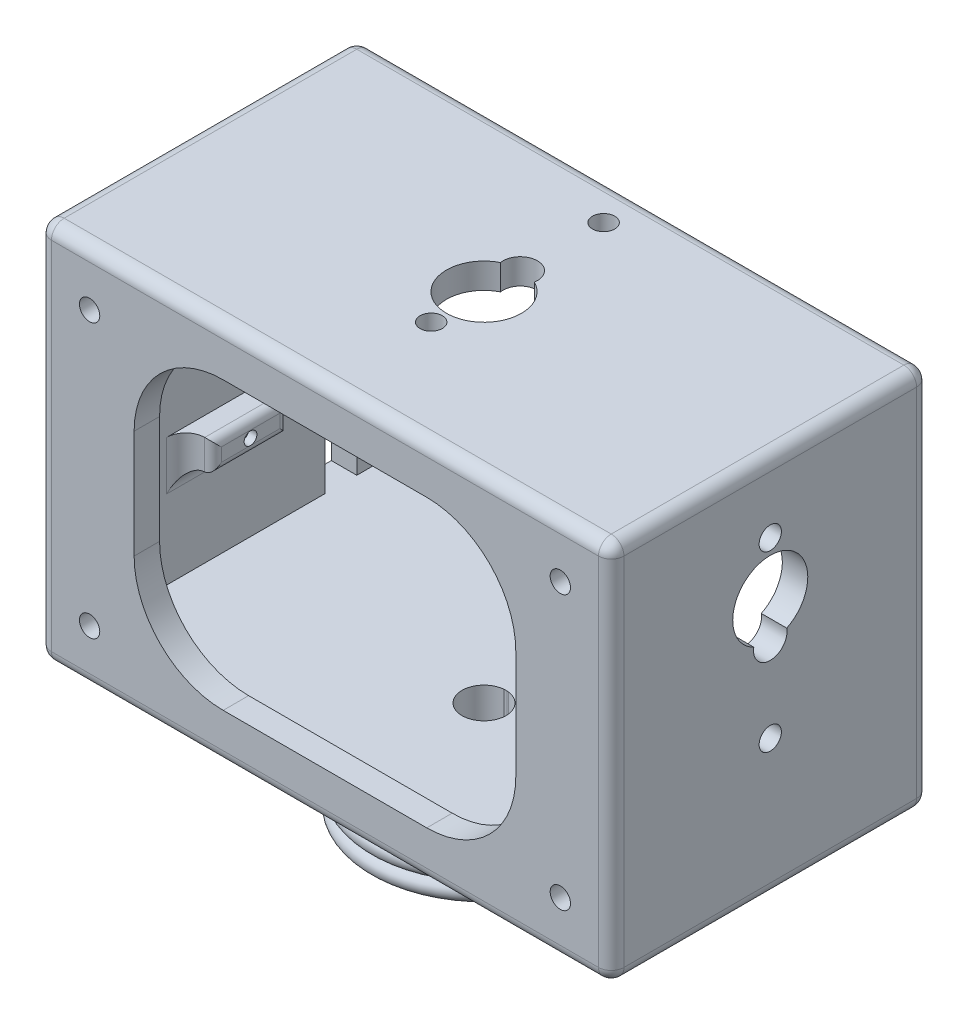
SolidWorks part; units mm, degrees
note: The reader was unsure of these and kept them because the rebuilt part matched: shared geometry of "Croquis1<4>", "Croquis5<4>", "Croquis5<5>", "Croquis7<3>", "Croquis8<3>", "Croquis16<3>", "Croquis16<4>", "Croquis16<5>".
other "Marca1"
sketch "Croquis19" plane through (-45, -41.0005, 0) normal (-0.2283, -0.8276, 0.5128) x (0.9733, -0.2073, 0.0987)
ref_plane "Alzado" through (0, 0, 0) normal (0, 0, 1) x (1, 0, 0)
ref_plane "Planta" through (0, 0, 0) normal (0, 1, 0) x (1, 0, 0)
ref_plane "Vista lateral" through (0, 0, 0) normal (1, 0, 0) x (0, 0, -1)
sketch "Croquis1" plane through (0, 0, 0) normal (0, 0, 1) x (1, 0, 0)
  line L0 (-41, 26) -> (-41, -26)
  line L1 (-45, 30) -> (45, 30)
  line L2 (-45, 30) -> (-45, -30)
  line L3 (-45, -30) -> (45, -30)
  line L4 (45, 30) -> (45, -30)
  line L5 (-45, -30) -> (45, -30)
  line L6 (-45, -30) -> (-45, -26)
  line L7 (-45, -26) -> (45, -26)
  line L8 (45, -30) -> (45, -26)
  line L9 (45, 30) -> (-45, 30)
  line L10 (45, 30) -> (45, 26)
  line L11 (45, 26) -> (-45, 26)
  line L12 (-45, 30) -> (-45, 26)
  line L15 (41, 26) -> (41, -26)
  point P4 (0, 30)
  point P6 (-45, 0)
  dimension "D1" = 60
  dimension "D2" = 90
  dimension "D3" = 4
  dimension "D4" = 4
  dimension "D5" = 4
  dimension "D6" = 4
extrude "Saliente-Extruir1" add sketch "Croquis1" against normal blind 4 contours L4 L11 L2 L7
extrude "Saliente-Extruir2" add sketch "Croquis1<4>" against normal blind 50 contours L11 L4 L1 L2 | L0 L11 L2 L7 | L11 L15 L7 L4 | L7 L2 L3 L4
sketch "Croquis1<4>" plane through (0, 0, 0) normal (0, 0, 1) x (1, 0, 0) same geometry as "Croquis1"
sketch "Croquis2" plane through (0, 0, 0) normal (1, 0, 0) x (0, 0, -1)
  line L0 (50, 30) -> (0, 30) construction
  line L1 (46, 26) -> (41, 26)
  line L2 (46, 26) -> (46, -26)
  line L3 (46, -26) -> (41, -26)
  line L4 (41, 26) -> (41, -26)
  line L5 (50, -30) -> (0, -30) construction
  line L6 (50, 30) -> (50, -30) construction
  dimension "D1" = 4
  dimension "D2" = 5
  dimension "D3" = 4
  dimension "D4" = 4
extrude "Cortar-Extruir1" cut sketch "Croquis2" along normal blind 88 from surface at -45 contours L2 L1 L4 L3 starting at face at (-45, 0, -25)
fillet "Redondeo1" radius 2 12 edges at (45, -30, -25) (0, -30, 0) (0, -30, -50) (-45, -30, -25) (-45, 30, -25) (0, 30, 0) (0, 30, -50) (45, 30, -25) (-45, 0, 0) (-45, 0, -50) (45, 0, 0) (45, 0, -50)
sketch "Croquis5" plane through (0, 0, 0) normal (1, 0, 0) x (0, 0, -1)
  line L0 (41, 26) -> (46, 26) construction
  line L1 (30.9, 21.3) -> (19.1, 21.3) construction
  line L2 (30.9, 21.3) -> (30.9, -10.6) construction
  line L3 (30.9, -10.6) -> (19.1, -10.6) construction
  line L4 (19.1, 21.3) -> (19.1, -10.6) construction
  line L5 (30.9, 16.6) -> (19.1, 16.6) construction
  line L6 (30.9, -5.9) -> (19.1, -5.9) construction
  line L9 (48, 28) -> (2, 28) construction
  line L10 (30.9, 21.3) -> (19.1, 21.3)
  line L11 (30.9, 21.3) -> (30.9, 16.6)
  line L12 (30.9, 16.6) -> (19.1, 16.6)
  line L13 (19.1, 21.3) -> (19.1, 16.6)
  line L14 (30.9, -10.6) -> (19.1, -10.6)
  line L15 (30.9, -10.6) -> (30.9, -5.9)
  line L16 (30.9, -5.9) -> (19.1, -5.9)
  line L17 (19.1, -10.6) -> (19.1, -5.9)
  arc A0 (27.5909, 5.3993) -> (22.4091, 5.3993) centre (25, 10.7) ccw
  circle A1 centre (25, 10.7) radius 2.4
  circle A2 centre (25, 10.7) radius 0.85
  circle A4 centre (25, 19) radius 1
  circle A5 centre (25, -8.3) radius 1
  arc A6 (22.4091, 5.3993) -> (27.5909, 5.3993) centre (25, 4.9326) ccw
  point P16 (0, 0)
  point P17 (0, 0)
  point P31 (25, -5.9)
  point P45 (25, 28)
  dimension "D6" = 4.8
  dimension "D7" = 1.7
  dimension "D8" = 14.3
  dimension "D10" = 2
  dimension "D11" = 2.3
  dimension "D12" = 2.3
  dimension "D1" = 31.9
  dimension "D2" = 11.8
  dimension "D3" = 4.7
  dimension "D4" = 4.7
  dimension "D5" = 4.7
  dimension "D13" = 11.8
extrude "Cortar-Extruir2" cut sketch "Croquis5" against normal through all both and the other way through all
extrude "Saliente-Extruir4" add sketch "Croquis5<4>" against normal blind 4.3 from surface at 41 contours L10 L13 L12 L11 A4 | L17 L14 L15 L16 A5 starting at face at (41, -9.3, -25)
sketch "Croquis5<4>" plane through (0, 0, 0) normal (1, 0, 0) x (0, 0, -1) same geometry as "Croquis5"
extrude "Saliente-Extruir5" add sketch "Croquis5<5>" along normal blind 4.3 from surface at -41 contours L10 L13 L12 L11 A4 | L17 L14 L15 L16 A5 starting at face at (-41, -9.3, -25)
sketch "Croquis5<5>" plane through (0, 0, 0) normal (1, 0, 0) x (0, 0, -1) same geometry as "Croquis5"
fillet "Redondeo3" radius 3 12 edges at (-41, -10.6, -25) (-41, 21.3, -25) (-41, -8.25, -19.1) (-41, -8.25, -30.9) (-41, 18.95, -30.9) (-41, 18.95, -19.1) (41, 18.95, -19.1) (41, -8.25, -19.1) (41, 21.3, -25) (41, -10.6, -25) (41, 18.95, -30.9) (41, -8.25, -30.9)
fillet "Redondeo4" radius 1.3 16 edges at (-36.7, 18.95, -30.9) (-36.7, -8.25, -30.9) (-36.7, -10.6, -25) (-36.7, -8.25, -19.1) (-36.7, -5.9, -25) (-36.7, 21.3, -25) (-36.7, 18.95, -19.1) (-36.7, 16.6, -25) (36.7, 18.95, -30.9) (36.7, 21.3, -25) (36.7, 16.6, -25) (36.7, 18.95, -19.1) (36.7, -8.25, -19.1) (36.7, -8.25, -30.9) (36.7, -10.6, -25) (36.7, -5.9, -25)
sketch "Croquis7" plane through (0, 0, 0) normal (1, 0, 0) x (0, 0, -1)
  circle A0 centre (25, 19) radius 1.75
  circle A1 centre (25, -8.3) radius 1.75
  dimension "D1" = 3.5
extrude "Cortar-Extruir3" cut sketch "Croquis7" against normal blind 7 from surface at 45 starting at face at (45, -8.3, -26)
extrude "Cortar-Extruir4" cut sketch "Croquis7<3>" along normal blind 7 from surface at -45 starting at face at (-45, -8.3, -26)
sketch "Croquis7<3>" plane through (0, 0, 0) normal (1, 0, 0) x (0, 0, -1) same geometry as "Croquis7"
sketch "Croquis8" plane through (0, 0, 0) normal (0, 1, 0) x (1, 0, 0)
  line L2 (0, 19.1) -> (0, 16.7) construction
  line L3 (0, 41.4) -> (0, 43.8) construction
  line L4 (43, 25) -> (-43, 25) construction
  line L5 (43, 2) -> (43, 48) construction
  line L6 (-43, 48) -> (-43, 2) construction
  line L7 (5.9, 41.4) -> (-5.9, 41.4)
  line L8 (5.9, 14.4) -> (-5.9, 14.4)
  line L9 (5.9, 14.4) -> (5.9, 19.1)
  line L10 (5.9, 19.1) -> (-5.9, 19.1)
  line L11 (-5.9, 14.4) -> (-5.9, 19.1)
  line L16 (5.9, 41.4) -> (5.9, 46.1)
  line L17 (5.9, 46.1) -> (-5.9, 46.1)
  line L18 (-5.9, 41.4) -> (-5.9, 46.1)
  line L20 (0, 41.4) -> (0, 46.1) construction
  arc A0 (-2.6646, 30.264) -> (2.6646, 30.264) centre (0, 25) ccw
  circle A2 centre (0, 16.7) radius 1
  circle A4 centre (0, 43.8) radius 0.75
  arc A5 (2.6646, 30.264) -> (-2.6646, 30.264) centre (0, 30.7) ccw
  point P2 (0, 0)
  point P4 (0, 0)
  point P12 (0, 25)
  point P30 (0, 46.1)
  point P33 (0, 14.4)
  dimension "D1" = 11.8
  dimension "D2" = 4.7
  dimension "D3" = 2.7
  dimension "D5" = 2
  dimension "D6" = 16.4
  dimension "D13" = 1.5
  dimension "D4" = 2.4
  dimension "D7" = 11.8
  dimension "D8" = 4.7
  dimension "D9" = 14.3
  dimension "D11" = 2.3
  dimension "D12" = 11.8
extrude "Cortar-Extruir5" cut sketch "Croquis8" against normal up to surface (4 mm away) from surface at 30 up to face at (-0.3333, 26, -38) starting at face at (0, 30, -25)
extrude "Saliente-Extruir6" add sketch "Croquis8<3>" against normal blind 4.3 from surface at 26 contours L18 L7 L16 L17 A4 | L11 L8 L9 L10 A2 starting at face at (0, 26, -43.05)
sketch "Croquis8<3>" plane through (0, 0, 0) normal (0, 1, 0) x (1, 0, 0) same geometry as "Croquis8"
fillet "Redondeo5" radius 3 6 edges at (5.9, 26, -16.75) (5.9, 26, -43.75) (0, 26, -46.1) (-5.9, 26, -16.75) (-5.9, 26, -43.75) (0, 26, -14.4)
fillet "Redondeo6" radius 1.3 8 edges at (5.9, 21.7, -43.75) (0, 21.7, -46.1) (-5.9, 21.7, -43.75) (5.9, 21.7, -16.75) (0, 21.7, -14.4) (-5.9, 21.7, -16.75) (0, 21.7, -19.1) (0, 21.7, -41.4)
sketch "Croquis9" plane through (0, 0, 0) normal (0, 1, 0) x (1, 0, 0)
  circle A0 centre (0, 43.8) radius 1.75
  circle A1 centre (0, 16.7) radius 1.75
  dimension "D1" = 3.5
extrude "Cortar-Extruir6" cut sketch "Croquis9" against normal blind 7 from surface at 30 starting at face at (0.75, 30, -43.8)
sketch "Croquis10" plane through (0, 0, 0) normal (0, 0, 1) x (1, 0, 0)
  line L0 (-36.7, 21.3) -> (-34.2, 21.3) construction
  line L2 (-34.2, 21.3) -> (-34.2, 16.6) construction
  line L3 (-34.2, 16.6) -> (-18.3, 16.6) construction
  line L4 (-18.3, 16.6) -> (-18.3, -5.9) construction
  line L5 (-18.3, -5.9) -> (-34.2, -5.9) construction
  line L6 (-34.2, -5.9) -> (-34.2, -10.6) construction
  line L7 (-34.2, -10.6) -> (-36.7, -10.6) construction
  line L8 (-36.7, -10.6) -> (-36.7, 21.3) construction
  line L9 (-5.9, 21.7) -> (-5.9, -8.2) construction
  line L10 (-5.9, -8.2) -> (5.9, -8.2) construction
  line L11 (5.9, -8.2) -> (5.9, 21.7) construction
  line L12 (5.9, 21.7) -> (-5.9, 21.7) construction
  line L13 (0, -27.5) -> (0, 27.5) construction
  line L14 (34.2, -10.6) -> (36.7, -10.6) construction
  line L15 (18.3, -5.9) -> (34.2, -5.9) construction
  line L16 (18.3, 16.6) -> (18.3, -5.9) construction
  line L17 (34.2, 16.6) -> (18.3, 16.6) construction
  line L18 (36.7, -10.6) -> (36.7, 21.3) construction
  line L19 (36.7, 21.3) -> (34.2, 21.3) construction
  line L20 (34.2, 21.3) -> (34.2, 16.6) construction
  line L22 (-36.7, 20) -> (-36.7, 17.9) construction
  line L23 (-38, 16.6) -> (-38, -5.9) construction
  line L24 (-41, 5.3993) -> (-41, 16.6) construction
  line L25 (-5.9, 23) -> (5.9, 23) construction
  line L26 (0, 21.7) -> (-4.6, 21.7) construction
  point P24 (-38, 5.35)
  point P27 (-36.7, 5.35)
  point P36 (0, 23)
  point P37 (0, 21.7)
  dimension "D1" = 4.7
  dimension "D2" = 22.5
  dimension "D3" = 2.5
  dimension "D4" = 22.7
  dimension "D5" = 11.8
  dimension "D6" = 29.9
sketch "Croquis11" plane through (0, 0, 0) normal (0, 0, 1) x (1, 0, 0)
  line L0 (43, 28) -> (-43, 28) construction
  line L5 (-16, -22.5) -> (16, -22.5)
  line L6 (-30, -8.5) -> (-30, 8.5)
  line L7 (-16, 22.5) -> (16, 22.5)
  line L8 (30, -8.5) -> (30, 8.5)
  line L9 (-30, -22.5) -> (30, 22.5) construction
  line L10 (-30, 22.5) -> (30, -22.5) construction
  line L11 (43, -28) -> (43, 28) construction
  line L12 (-43, 28) -> (-43, -28) construction
  line L13 (-43, -28) -> (43, -28) construction
  arc A0 (16, -22.5) -> (30, -8.5) centre (16, -8.5) ccw
  arc A1 (16, 22.5) -> (30, 8.5) centre (16, 8.5) cw
  arc A2 (-16, -22.5) -> (-30, -8.5) centre (-16, -8.5) cw
  arc A3 (-30, 8.5) -> (-16, 22.5) centre (-16, 8.5) cw
  circle A4 centre (-37, 21.5) radius 1.6
  circle A5 centre (37, 21.5) radius 1.6
  circle A6 centre (37, -21.5) radius 1.6
  circle A7 centre (-37, -21.5) radius 1.6
  point P0 (0, 0)
  dimension "D1" = 14
  dimension "D4" = 6.5
  dimension "D5" = 6
  dimension "D6" = 6
  dimension "D7" = 6.5
  dimension "D8" = 3.2
  dimension "D2" = 60
  dimension "D3" = 45
extrude "Cortar-Extruir7" cut sketch "Croquis11" against normal up to next contours A7 | A3 L6 A2 L5 A0 L8 A1 L7 | A4 | A5 | A6
ref_plane "Plano2" through (0, 0, -25) normal (0, 0, 1) x (1, 0, 0)
sketch "Croquis14" plane through (0, 0, -25) normal (0, 0, 1) x (1, 0, 0)
  line L1 (43, -30) -> (-43, -30) construction
  line L6 (0, -30) -> (16.6119, -30)
  line L7 (0, -41) -> (16.6119, -41)
  line L9 (0, -30) -> (0, -41)
  arc A0 (16.6119, -41) -> (16.6119, -38.2964) centre (16.6477, -39.6482) ccw
  arc A1 (16.6119, -38.2964) -> (16.6119, -35.5) centre (16.5748, -36.8982) ccw
  arc A2 (16.6119, -35.5) -> (16.6119, -32.7964) centre (16.6477, -34.1482) ccw
  arc A3 (16.6119, -32.7964) -> (16.6119, -30) centre (16.5748, -31.3982) ccw
  point P1 (18, -39.6482)
  dimension "D1" = 11
  dimension "D2" = 18
revolve "Revolución2" add sketch "Croquis14" angle 360 about L9
sketch "Croquis16" plane through (0, 0, 0) normal (0, 1, 0) x (1, 0, 0)
  line L0 (-16.5, 25) -> (16.5, 25) construction
  line L1 (0, 21.55) -> (0, 25) construction
  line L2 (45, 2) -> (45, 48) construction
  line L3 (-0.2106, 21.5564) -> (-14.4893, 22.8057)
  line L4 (-0.2106, 28.4436) -> (-14.4893, 27.1943)
  line L5 (0.2106, 21.5564) -> (14.4893, 22.8057)
  line L6 (0.2106, 28.4436) -> (14.4893, 27.1943)
  line L7 (0, 25) -> (0, 27) construction
  circle A0 centre (0, 25) radius 3.45
  arc A2 (-14.4893, 22.8057) -> (-14.4893, 27.1943) centre (-14.2973, 25) cw
  arc A3 (14.4893, 22.8057) -> (14.4893, 27.1943) centre (14.2973, 25) ccw
  circle A4 centre (0, 25) radius 1.5
  point P4 (0, 25)
  point P8 (45, 25)
  dimension "D6" = 3
  dimension "D1" = 33
  dimension "D2" = 3.45
  dimension "D4" = 10
  dimension "D7" = 2
extrude "Cortar-Extruir8" cut sketch "Croquis16" along normal blind 5 from surface contours A4
extrude "Cortar-Extruir9" cut sketch "Croquis16<3>" along normal blind 4 from surface contours A0 A4
sketch "Croquis16<3>" plane through (0, 0, 0) normal (0, 1, 0) x (1, 0, 0) same geometry as "Croquis16"
extrude "Cortar-Extruir10" cut sketch "Croquis16<4>" along normal blind 1.5 from surface contours L5 A3 L6 A0 | A2 L3 A0 L4
sketch "Croquis16<4>" plane through (0, 0, 0) normal (0, 1, 0) x (1, 0, 0) same geometry as "Croquis16"
sketch "Croquis17" plane through (0, 0, 0) normal (1, 0, 0) x (0, 0, -1)
  line L0 (25, 30) -> (25, 10.7) construction
  line L1 (2, 30) -> (48, 30) construction
sketch "Croquis18" plane through (0, -26, 0) normal (0, 1, 0) x (1, 0, 0)
  line L12 (41, 4) -> (41, 41)
  line L13 (41, 41) -> (43, 41)
  line L14 (43, 41) -> (43, 46)
  line L15 (43, 46) -> (41, 46)
  line L16 (41, 46) -> (41, 50)
  line L17 (41, 50) -> (-41, 50)
  line L18 (-41, 50) -> (-41, 46)
  line L19 (-41, 46) -> (-45, 46)
  line L20 (-45, 46) -> (-45, 41)
  line L21 (-45, 41) -> (-41, 41)
  line L22 (-41, 41) -> (-41, 4)
  line L23 (-41, 4) -> (41, 4)
  line L24 (41, 4) -> (41, 41)
  line L25 (41, 41) -> (43, 41)
  line L26 (43, 41) -> (43, 46)
  line L27 (43, 46) -> (41, 46)
  line L28 (41, 46) -> (41, 50)
  line L29 (41, 50) -> (-41, 50)
  line L30 (-41, 50) -> (-41, 46)
  line L31 (-41, 46) -> (-45, 46)
  line L32 (-45, 46) -> (-45, 41)
  line L33 (-45, 41) -> (-41, 41)
  line L34 (-41, 41) -> (-41, 4)
  line L35 (-41, 4) -> (41, 4)
  circle A0 centre (0, 25) radius 1.5 construction
  circle A1 centre (0, 25) radius 1.5
  dimension "D1" = 0
extrude "Cortar-Extruir11" cut sketch "Croquis18" against normal through all contours A1
extrude "Cortar-Extruir12" cut sketch "Croquis16<5>" against normal blind 10 from surface at -26 contours A0 A4
sketch "Croquis16<5>" plane through (0, 0, 0) normal (0, 1, 0) x (1, 0, 0) same geometry as "Croquis16"
